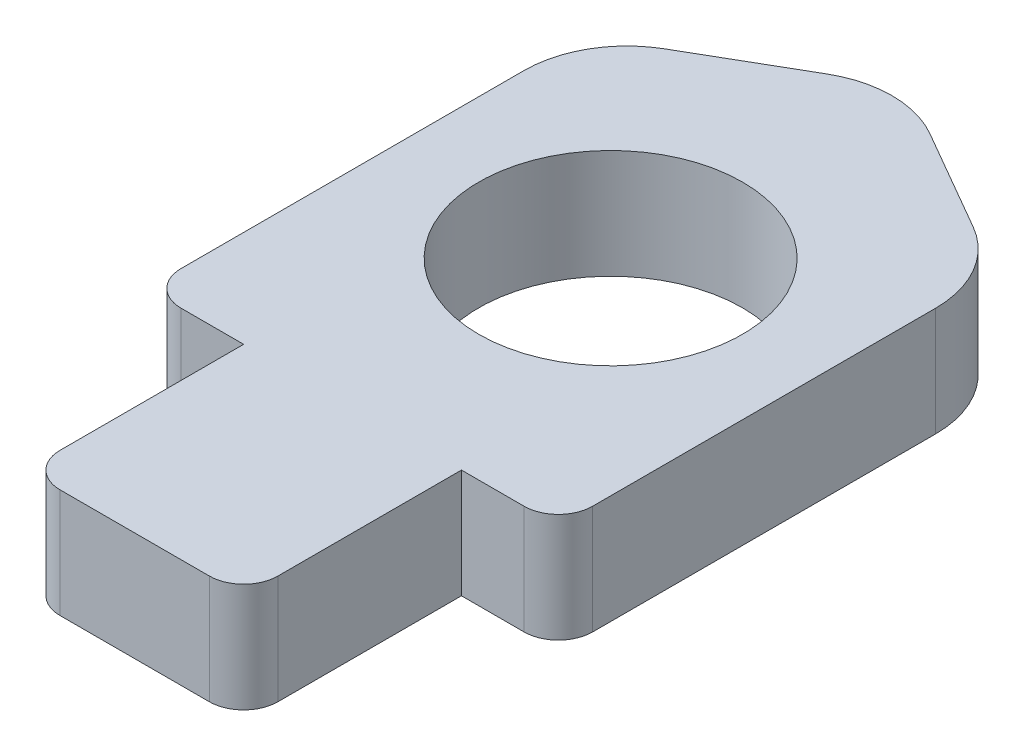
SolidWorks part; units mm, degrees
material "Beech"
ref_plane "Front Plane" through (0, 0, 0) normal (0, 0, 1) x (1, 0, 0)
ref_plane "Top Plane" through (0, 0, 0) normal (0, 1, 0) x (1, 0, 0)
ref_plane "Right Plane" through (0, 0, 0) normal (1, 0, 0) x (0, 0, -1)
sketch "Sketch2" plane through (0, 0, 0) normal (0, 1, 0) x (1, 0, 0)
  line L0 (-6, 5.205) -> (-5.4495, 5.205)
  line L1 (-6, 3.4729) -> (-6, -7.5237)
  line L2 (6, 3.4729) -> (6, -7.5237)
  line L3 (-6, -7.5237) -> (-3.175, -7.5237)
  line L4 (-4.5, 6.071) -> (-1.5, 7.8031)
  line L5 (-3.175, -7.5237) -> (-3.175, -13.8737)
  line L6 (-3.175, -13.8737) -> (3.175, -13.8737)
  line L7 (3.175, -13.8737) -> (3.175, -7.5237)
  line L8 (1.5, 7.8031) -> (4.5, 6.071)
  line L9 (3.175, -7.5237) -> (6, -7.5237)
  line L12 (5.4495, 5.205) -> (6, 5.205)
  circle A0 centre (0, 0) radius 3.845
  arc A1 (-4.5, 6.071) -> (-6, 3.4729) centre (-3, 3.4729) ccw
  arc A2 (4.5, 6.071) -> (6, 3.4729) centre (3, 3.4729) cw
  arc A3 (1.5, 7.8031) -> (-1.5, 7.8031) centre (0, 5.205) ccw
  point P3 (0, 5.205)
  point P14 (0, -13.8737)
  dimension "D1" = 7.69
  dimension "D9" = 3
  dimension "D10" = 3
  dimension "D11" = 3
  dimension "D2" = 5.205
  dimension "D3" = 12.7287
  dimension "D4" = 12
  dimension "D5" = 6.35
  dimension "D6" = 6.35
  dimension "D8" = 30
extrude "Boss-Extrude1" add sketch "Sketch2" along normal blind 3.175 contours L8 A3 L4 A1 L1 L5 L2 A2 A0 region at (-5.6196, 0, -4.3055)
fillet "Fillet1" radius 1 4 edges at (6, 1.5875, 7.5237) (-6, 1.5875, 7.5237) (-3.175, 1.5875, 13.8737) (3.175, 1.5875, 13.8737)
equation "\"CageLeftBottomEdge\"=22.11mm"
equation "\"CageLeftTopEdge\"=22.11mm"
equation "\"CageRightBottomEdge\"=21.63mm"
equation "\"CageRightTopEdge\"=21.63mm"
equation "\"CageHeight\"=86.04mm"
equation "\"CageLength\"=73.76mm"
equation "\"CageTopScrewClearance\"=10mm"
equation "\"CageBottomScrewClearance\"=25mm"
equation "\"CageLeftTopDepth\"= 11.65mm"
equation "\"CageLeftBottomDepth\"=11.11mm"
equation "\"CageLeftTopHeight\"=8.56175mm"
equation "\"CageLeftBottomHeight\"=16mm"
equation "\"CageRightTopDepth\"= 11.05mm"
equation "\"CageRightBottomDepth\"=10.58mm"
equation "\"CageRightTopHeight\"=9.6mm"
equation "\"CageRightBottomHeight\"=15.49mm"
equation "\"CageLeftTopChannelDepth\"=2.41908mm"
equation "\"CageLeftBottomChannelDepth\"=2.588mm"
equation "\"CageLeftChannelHeight\"=11.7mm"
equation "\"CageRightTopChannelDepth\"=2.32mm"
equation "\"CageRightBottomChannelDepth\"=2.318mm"
equation "\"CageRightChannelHeight\"=10mm"
equation "\"CageChanRelHeight\"=23.99mm"
equation "\"CageChanRelDepth\"=5.492mm"
equation "\"CageChamberRadius\"=16.261mm"
equation "\"CageScrewDiameter\"=4.8mm"
equation "\"CageSetScrewDiameter\"=3.5mm"
equation "\"CageAxleRadius\"=6.639mm"
equation "\"CageAxleKeyHeight\"=1.619mm"
equation "\"CageAxleKeyWidth\"=2.662mm"
equation "\"CageHoseWindowWidth\"=16.29mm"
equation "\"CageHoseWindowHeight\"=26.5mm"
equation "\"CageHoseWindow-Edge\"=8.89mm"
equation "\"CageScrew-VerticalEdge\"=5.0mm"
equation "\"CageScrew-HorizontalEdge\"=7.5mm"
equation "\"CageScrew-HoseCornerScrewEdge\"=4.45mm"
equation "\"CageAxle-BottomEdge\"=56.05mm"
equation "\"CageAxle-FrontEdge\"=46.03mm"
equation "\"CageBackSetScrew-Axle\"=40mm"
equation "\"CageFrontSetScrew-Axle\"=22mm"
equation "\"CageVelocityWindow-BackEdge\"=34.8mm"
equation "\"CageVelocityWindow-BottomEdge\"=27.55mm"
equation "\"CageVelocityWindowHeight\"=22.29mm"
equation "\"CageVelocityWindowWidth\"=12.61mm"
equation "\"TriggerSlot-BottomEdge\"=6.35mm"
equation "\"TriggerSlot-FrontEdge\"=15mm"
equation "\"TriggerSlotSize\"=6.7mm"
equation "\"vigorwidth\"= 0.472441in"
equation "\"vigorflangewidth\"= 0.731102in"
equation "\"vigorflangelength\"= 0.131102in"
equation "\"vigorscrewsize\"= 0.066535in"
equation "\"vigorholeoffsetwid\"= 0.0646653in"
equation "\"vigorholeoffsetlen\"= 0.065551in"
equation "\"vigorflangedepth\"= 0.0901575in"
equation "\"vigordiscdepth\"= 0.0492126in"
equation "\"vigormotordepth\"= 1.12362in"
equation "\"vigortipdepth\"= 0.259055in"
equation "\"vigoraxlewidth\"= 0.173622in"
equation "\"vigorcutlen\"= 0.0480315in"
equation "\"vigoraxledepth\"= 0.159055in"
equation "\"TriggerRackOffset\"=.236224in"
equation "\"TriggerSlotSizeInt\"=.25in"
equation "\"MotorMountLegLength\"=.25in"
equation "\"GearOffset\"=.264907in"
equation "\"TriggerSlotSpacing\"=.25in"
equation "\"TGMGearFaceDiameter\"=24.40mm"
equation "\"TGMCylinderLength\"=15.00mm"
equation "\"TGMScrewHole-Center\"=8.70mm"
equation "\"TGMScrewHoleDiameter\"=5.04mm"
equation "\"TGMCenterHoleDiameter\"=9.50mm"
equation "\"TGMShaftCollarSideLength\"=19.00mm"
equation "\"TGMShaftCollarDockingDepth\"=7.00mm"
equation "\"whitemotordepth\"=11.27mm"
equation "\"whitemotorbackdepth\"=3.845mm"
equation "\"whitemotoraxledepth\" = 3.5mm"
equation "\"whitemotoraxleoffset\"=11.4mm"
equation "\"whitemotorwidth\"=12.07mm"
equation "\"whitemotorheight\"=16.68mm"
equation "\"whitemotorcylinderlength\" =13.04mm"
equation "\"whitemotorcylinderradius\"=3.845mm"
equation "\"whitemotorcylinderoffset\"=2.35mm"
equation "\"whitemotorcutoutlength\"=1.88mm"
equation "\"whitemotorouterrad\"=5mm"
equation "\"whitemotorinnerrad\"=2.95mm"
equation "\"D1@Sketch2\"=\"whitemotorcylinderradius\"*2"
equation "\"D2@Sketch2\"=\"whitemotoraxleoffset\"-\"whitemotorcylinderradius\"-\"whitemotorcylinderoffset\""
equation "\"D3@Sketch2\"=\"TriggerRackOffset\"+\"GearOffset\""
equation "\"D5@Sketch2\"=\"MotorMountLegLength\""
equation "\"D6@Sketch2\"=\"TriggerSlotSpacing\""
equation "\"D4@Sketch2\"=12mm"
